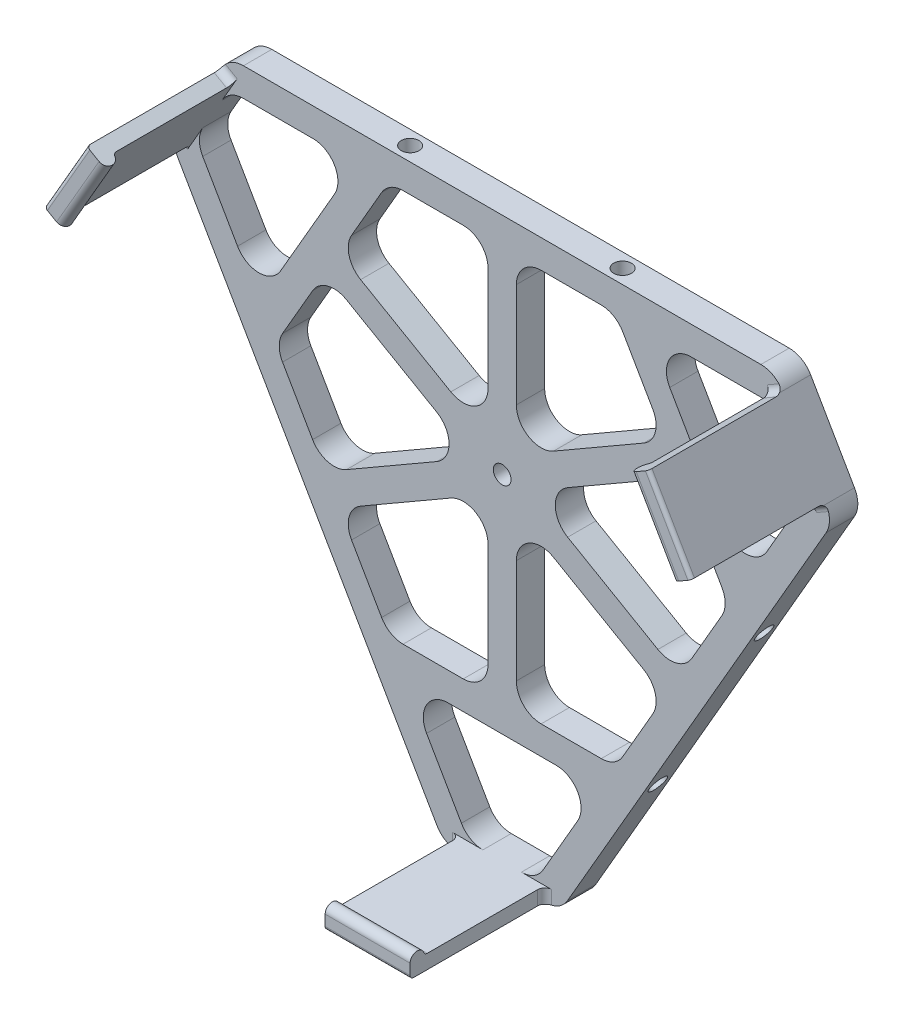
SolidWorks part; units mm, degrees
ref_plane "Front Plane" through (0, 0, 0) normal (0, 0, 1) x (1, 0, 0)
ref_plane "Top Plane" through (0, 0, 0) normal (0, 1, 0) x (1, 0, 0)
ref_plane "Right Plane" through (0, 0, 0) normal (1, 0, 0) x (0, 0, -1)
sketch "Sketch1" plane through (0, 0, 0) normal (0, 0, 1) x (1, 0, 0)
  line L0 (0, 31.7387) -> (0, -49.2613) construction
  line L1 (-16.898, -49.2613) -> (16.898, -49.2613) construction
  line L2 (-2, 3.4641) -> (-2, 27.7387)
  line L3 (-4, 0) -> (-25.0224, -12.1373)
  line L4 (-2, 3.4641) -> (-23.0224, 15.6014)
  line L5 (0, 31.7387) -> (-38.5577, 31.7387)
  line L6 (2, 27.7387) -> (16.015, 27.7387)
  line L7 (-2, 27.7387) -> (-16.015, 27.7387)
  line L8 (0, 31.7387) -> (38.5577, 31.7387)
  line L9 (-8.2077, -49.2613) -> (8.2077, -49.2613)
  line L10 (2, 3.4641) -> (23.0224, 15.6014)
  line L11 (25.0224, 12.1373) -> (32.0299, 0)
  line L12 (27.4865, 15.8694) -> (34.3393, 4)
  line L13 (27.4865, 15.8694) -> (20.6338, 27.7387)
  line L14 (23.0224, 15.6014) -> (16.015, 27.7387)
  line L15 (13.7056, -31.7387) -> (4.7436, -47.2613)
  line L16 (4, 0) -> (25.0224, -12.1373)
  line L17 (23.0224, -15.6014) -> (16.015, -27.7387)
  line L18 (27.4865, -15.8694) -> (8.2077, -49.2613)
  line L19 (27.4865, -15.8694) -> (46.7654, 17.5226)
  line L20 (25.0224, -12.1373) -> (32.0299, 0)
  line L21 (-2, -3.4641) -> (-2, -27.7387)
  line L22 (2, -3.4641) -> (2, -27.7387)
  line L23 (-2, -27.7387) -> (-16.015, -27.7387)
  line L24 (0, -31.7387) -> (-13.7056, -31.7387)
  line L25 (0, -31.7387) -> (13.7056, -31.7387)
  line L26 (2, -27.7387) -> (16.015, -27.7387)
  line L27 (4.7436, -47.2613) -> (-4.7436, -47.2613)
  line L28 (-2, -3.4641) -> (-23.0224, -15.6014)
  line L29 (-25.0224, -12.1373) -> (-32.0299, 0)
  line L30 (-27.4865, -15.8694) -> (-46.7654, 17.5226)
  line L31 (-27.4865, -15.8694) -> (-8.2077, -49.2613)
  line L32 (-23.0224, -15.6014) -> (-16.015, -27.7387)
  line L33 (-13.7056, -31.7387) -> (-4.7436, -47.2613)
  line L34 (-4, 0) -> (-25.0224, 12.1373)
  line L35 (-23.0224, 15.6014) -> (-16.015, 27.7387)
  line L36 (-27.4865, 15.8694) -> (-20.6338, 27.7387)
  line L37 (-27.4865, 15.8694) -> (-34.3393, 4)
  line L38 (-25.0224, 12.1373) -> (-32.0299, 0)
  line L39 (2, 3.4641) -> (2, 27.7387)
  line L40 (4, 0) -> (25.0224, 12.1373)
  line L41 (2, -3.4641) -> (23.0224, -15.6014)
  line L42 (27.4865, -15.8694) -> (-42.6615, 24.6306) construction
  line L43 (-46.7654, 17.5226) -> (-38.5577, 31.7387)
  line L44 (-27.4865, -15.8694) -> (42.6615, 24.6306) construction
  line L45 (-43.3013, 19.5226) -> (-38.5577, 27.7387)
  line L46 (-34.3393, 4) -> (-43.3013, 19.5226)
  line L47 (-20.6338, 27.7387) -> (-38.5577, 27.7387)
  line L48 (52.2416, 8.0375) -> (33.0814, 41.2238) construction
  line L49 (38.5577, 31.7387) -> (46.7654, 17.5226)
  line L50 (38.5577, 27.7387) -> (43.3013, 19.5226)
  line L51 (34.3393, 4) -> (43.3013, 19.5226)
  line L52 (20.6338, 27.7387) -> (38.5577, 27.7387)
  circle A0 centre (0, 0) radius 1.25
  point P7 (0, -49.2613)
  point P45 (-42.6615, 24.6306)
  point P52 (42.6615, 24.6306)
  point P81 (0, 0)
  dimension "D6" = 6
extrude "Boss-Extrude4" add sketch "Sketch1" along normal blind 4
fillet "Fillet1" radius 3.5 42 edges at (-23.0224, 15.6014, 2) (-16.015, 27.7387, 2) (-2, 27.7387, 2) (-2, 3.4641, 2) (2, 3.4641, 2) (2, 27.7387, 2) (16.015, 27.7387, 2) (23.0224, 15.6014, 2) (25.0224, 12.1373, 2) (4, 0, 2) (25.0224, -12.1373, 2) (32.0299, 0, 2) (23.0224, -15.6014, 2) (2, -3.4641, 2) (2, -27.7387, 2) (16.015, -27.7387, 2) (-23.0224, -15.6014, 2) (-16.015, -27.7387, 2) (-2, -27.7387, 2) (-2, -3.4641, 2) (-25.0224, -12.1373, 2) (-4, 0, 2) (-25.0224, 12.1373, 2) (-32.0299, 0, 2) (8.2077, -49.2613, 2) (-8.2077, -49.2613, 2) (-13.7056, -31.7387, 2) (13.7056, -31.7387, 2) (4.7436, -47.2613, 2) (-4.7436, -47.2613, 2) (-34.3393, 4, 2) (-43.3013, 19.5226, 2) (-38.5577, 27.7387, 2) (-20.6338, 27.7387, 2) (34.3393, 4, 2) (20.6338, 27.7387, 2) (43.3013, 19.5226, 2) (38.5577, 27.7387, 2) (46.7654, 17.5226, 2) (38.5577, 31.7387, 2) (-38.5577, 31.7387, 2) (-46.7654, 17.5226, 2)
sketch "Sketch3" plane through (-27.4865, -15.8694, 0) normal (-0.866, -0.5, 0) x (0, 0, 1)
  line L0 (0, 0) -> (4, 0) construction
  line L1 (4, 36.537) -> (4, -36.537) construction
  line L2 (2, 0) -> (2, 15)
  circle A0 centre (2, 15) radius 1.25
  circle A1 centre (2, -15) radius 1.25
extrude "Cut-Extrude1" cut sketch "Sketch3" against normal blind 3 contours A0 | A1 region at (-34.5571, -3.6228, 2.8589) region at (-19.9865, -28.8597, 2)
pattern_circular "CirPattern1" count 3 every 120 about axis through (0, 0, 4) along (0, 0, 1) of "Cut-Extrude1"
sketch "Sketch4" plane through (0, 0, 4) normal (0, 0, 1) x (1, 0, 0)
  line L0 (-40.9295, 23.6306) -> (-42.6615, 24.6306)
  line L1 (-39.568, 25.9887) -> (-42.2909, 21.2726) construction
  line L2 (-39.568, 29.9887) -> (-45.755, 19.2726) construction
  line L3 (-37.9295, 28.8268) -> (-39.6615, 29.8268)
  line L4 (-43.9295, 18.4345) -> (-45.6615, 19.4345)
  line L5 (-45.6615, 19.4345) -> (-39.6615, 29.8268)
  line L6 (-43.9295, 18.4345) -> (-37.9295, 28.8268)
  line L7 (40.9295, 23.6306) -> (42.6615, 24.6306)
  line L8 (43.9295, 18.4345) -> (45.6615, 19.4345)
  line L9 (37.9295, 28.8268) -> (39.6615, 29.8268)
  line L10 (39.6615, 29.8268) -> (45.6615, 19.4345)
  line L11 (37.9295, 28.8268) -> (43.9295, 18.4345)
  line L12 (0, -47.2613) -> (0, -49.2613)
  line L13 (-6, -47.2613) -> (-6, -49.2613)
  line L14 (6, -47.2613) -> (6, -49.2613)
  line L15 (6, -49.2613) -> (-6, -49.2613)
  line L16 (6, -47.2613) -> (-6, -47.2613)
  point P25 (0, 0)
  dimension "D1" = 6
  dimension "D2" = 6
  dimension "D3" = 3
extrude "Boss-Extrude5" add sketch "Sketch4" along normal blind 19 contours L7 L11 L8 L10 | L9 L11 L7 L10 | L0 L6 L3 L5 | L4 L6 L0 L5 | L14 L16 L12 L15 | L12 L16 L13 L15 region at (-43.2955, 21.5326, 4) region at (-40.2955, 26.7287, 4) region at (40.2955, 26.7287, 4) region at (43.2955, 21.5326, 4) region at (3, -48.2613, 4) region at (-3, -48.2613, 4)
sketch "Sketch5" plane through (6, 0, 0) normal (1, 0, 0) x (0, 0, -1)
  line L0 (-23, -47.2613) -> (-22, -47.2613)
  line L1 (-23, -47.2613) -> (-4, -47.2613) construction
  circle A0 centre (-22, -47.2613) radius 1
  line M2 (-4, -47.2613) -> (-23, -47.2613)
extrude "Boss-Extrude6" add sketch "Sketch5" against normal blind 12 contours A0 M2 region at (6, -46.8369, 22)
sketch "Sketch6" plane through (-3, -5.1962, 0) normal (-0.5, -0.866, 0) x (0.866, -0.5, 0)
  line L0 (-47.2613, 23) -> (-47.2613, 22)
  line L1 (-47.2613, 23) -> (-47.2613, 4) construction
  circle A0 centre (-47.2613, 22) radius 1
  line M3 (-47.2613, 4) -> (-47.2613, 23)
extrude "Boss-Extrude7" add sketch "Sketch6" against normal blind 12 contours A0 M3 region at (-43.5619, 18.2223, 22)
sketch "Sketch7" plane through (-3, 5.1962, 0) normal (-0.5, 0.866, 0) x (0.866, 0.5, 0)
  line L0 (47.2613, -23) -> (47.2613, -22)
  line L1 (47.2613, -23) -> (47.2613, -4) construction
  circle A0 centre (47.2613, -22) radius 1
  line M3 (47.2613, -4) -> (47.2613, -23)
extrude "Boss-Extrude8" add sketch "Sketch7" against normal blind 12 contours A0 M3 region at (37.5619, 28.6146, 22)
fillet "Fillet2" radius 0.5 6 edges at (40.9295, 23.6306, 21) (42.6615, 24.6306, 23) (0, -47.2613, 21) (0, -49.2613, 23) (-42.6615, 24.6306, 23) (-40.9295, 23.6306, 21)
fillet "Fillet3" radius 1 6 edges at (44.7955, 18.9345, 4) (-44.7955, 18.9345, 4) (6, -48.2613, 4) (-6, -48.2613, 4) (-38.7955, 29.3268, 4) (38.7955, 29.3268, 4)
